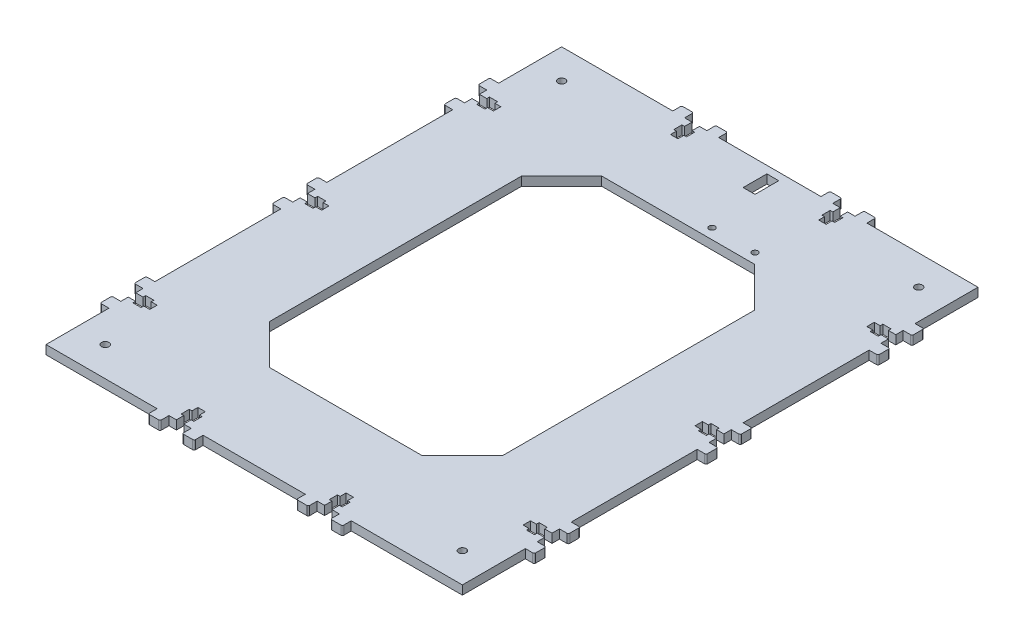
SolidWorks part; units mm, degrees
ref_plane "Plan de face" through (0, 0, 0) normal (0, 0, 1) x (1, 0, 0)
ref_plane "Plan de dessus" through (0, 0, 0) normal (0, 1, 0) x (1, 0, 0)
ref_plane "Plan de droite" through (0, 0, 0) normal (1, 0, 0) x (0, 0, -1)
sketch "Esquisse2" plane through (0, 0, 0) normal (0, 1, 0) x (1, 0, 0)
  line L16 (0, 0) -> (0, -31.3635) construction
  line L23 (-140.5, 174) -> (0, 174)
  line L24 (-140.5, 174) -> (-140.5, 0)
  line L25 (-140.5, 0) -> (-78.5, 0)
  line L26 (0, 174) -> (0, 112)
  line L27 (-140.5, 174) -> (0, 0) construction
  line L28 (-140.5, 0) -> (0, 174) construction
  line L29 (0, 0) -> (25.964, 0) construction
  line L30 (0, 112) -> (-78.5, 112)
  line L31 (-78.5, 112) -> (-78.5, 0)
  circle A4 centre (-120.5, 154) radius 2.5
  point P28 (-70.25, 87)
  dimension "D11" = 348
  dimension "D17" = 5
  dimension "D8" = 20
  dimension "D9" = 20
  dimension "D10" = 281
  dimension "D16" = 62
extrude "plaque" add sketch "Esquisse2" along normal mid plane 6
sketch "Esquisse10" plane through (0, 3, 0) normal (0, 1, 0) x (1, 0, 0)
  line L0 (-140.5, 174) -> (-140.5, 0) construction
  line L2 (0, 174) -> (-140.5, 174) construction
  line B0 (-140.5, 100.5) -> (-145.5, 100.5)
  line B1 (-146.5, 101.5) -> (-146.5, 107.5)
  line B2 (-145.5, 108.5) -> (-140.5, 108.5)
  line B3 (-140.5, 108.5) -> (-140.5, 113.5)
  line B4 (-140.5, 113.5) -> (-135.5, 113.5)
  line B5 (-135.5, 113.5) -> (-135.5, 111.7)
  line B6 (-135.5, 111.7) -> (-130, 111.7)
  line B7 (-130, 111.7) -> (-130, 113.5)
  line B8 (-130, 113.5) -> (-126, 113.5)
  line B9 (-126, 113.5) -> (-126, 118.5)
  line B10 (-126, 116) -> (-140.5, 116) construction
  line B11 (-140.5, 131.5) -> (-140.5, 123.5)
  line B12 (-140.5, 108.5) -> (-140.5, 100.5)
  line B13 (-130, 118.5) -> (-126, 118.5)
  line B14 (-130, 120.3) -> (-130, 118.5)
  line B15 (-135.5, 120.3) -> (-130, 120.3)
  line B16 (-135.5, 118.5) -> (-135.5, 120.3)
  line B17 (-140.5, 118.5) -> (-135.5, 118.5)
  line B18 (-140.5, 123.5) -> (-140.5, 118.5)
  line B19 (-145.5, 123.5) -> (-140.5, 123.5)
  line B20 (-146.5, 130.5) -> (-146.5, 124.5)
  line B21 (-140.5, 131.5) -> (-145.5, 131.5)
  line B22 (-140.5, 113.5) -> (-140.5, 118.5)
  arc B23 (-146.5, 107.5) -> (-145.5, 108.5) centre (-145.5, 107.5) cw
  arc B24 (-145.5, 100.5) -> (-146.5, 101.5) centre (-145.5, 101.5) cw
  arc B25 (-145.5, 131.5) -> (-146.5, 130.5) centre (-145.5, 130.5) ccw
  arc B26 (-146.5, 124.5) -> (-145.5, 123.5) centre (-145.5, 124.5) ccw
  line B27 (-65.5, 174) -> (-65.5, 179)
  line B28 (-64.5, 180) -> (-58.5, 180)
  line B29 (-57.5, 179) -> (-57.5, 174)
  line B30 (-57.5, 174) -> (-52.5, 174)
  line B31 (-52.5, 174) -> (-52.5, 169)
  line B32 (-52.5, 169) -> (-54.3, 169)
  line B33 (-54.3, 169) -> (-54.3, 163.5)
  line B34 (-54.3, 163.5) -> (-52.5, 163.5)
  line B35 (-52.5, 163.5) -> (-52.5, 159.5)
  line B36 (-52.5, 159.5) -> (-47.5, 159.5)
  line B37 (-50, 159.5) -> (-50, 174) construction
  line B38 (-34.5, 174) -> (-42.5, 174)
  line B39 (-57.5, 174) -> (-65.5, 174)
  line B40 (-47.5, 163.5) -> (-47.5, 159.5)
  line B41 (-45.7, 163.5) -> (-47.5, 163.5)
  line B42 (-45.7, 169) -> (-45.7, 163.5)
  line B43 (-47.5, 169) -> (-45.7, 169)
  line B44 (-47.5, 174) -> (-47.5, 169)
  line B45 (-42.5, 174) -> (-47.5, 174)
  line B46 (-42.5, 179) -> (-42.5, 174)
  line B47 (-35.5, 180) -> (-41.5, 180)
  line B48 (-34.5, 174) -> (-34.5, 179)
  line B49 (-52.5, 174) -> (-47.5, 174)
  arc B50 (-58.5, 180) -> (-57.5, 179) centre (-58.5, 179) cw
  arc B51 (-65.5, 179) -> (-64.5, 180) centre (-64.5, 179) cw
  arc B52 (-34.5, 179) -> (-35.5, 180) centre (-35.5, 179) ccw
  arc B53 (-41.5, 180) -> (-42.5, 179) centre (-41.5, 179) ccw
  line M1 (-140.5, 174) -> (-140.5, 0)
  line M6 (0, 174) -> (-140.5, 174)
  dimension "D1" = 58
  dimension "D2" = 50
sketch_block_instance "Bloc4-17"
sketch_block "Bloc4" parameters "D7"=1, "D1"=5, "D2"=5, "D3"=5.5, "D4"=1.8, "D5"=4, "D6"=2.5
sketch_block_instance "Bloc4-29"
extrude "Boss.-Extru.8" add sketch "Esquisse10" against normal blind 6 contours B20 B26 B19 B21 B25 M1 | B24 B0 B2 B23 B1 M1 | B51 B27 B29 B50 B28 M6 | B47 B53 B46 B48 B52 M6 region at (-38.5, 3, -176.9749) region at (-61.5, 3, -176.9749) region at (-143.4749, 3, -127.5) region at (-143.4749, 3, -104.5)
extrude "Enlèv. mat.-Extru.8" cut sketch "Esquisse10<3>" against normal blind 6 contours B17 B4 B5 B6 B7 B8 B9 B13 B14 B15 B16 M1 | B44 B31 B32 B33 B34 B35 B36 B40 B41 B42 B43 M6 region at (-50, 3, -166.6427) region at (-133.1427, 3, -116)
sketch "Esquisse10<3>" plane through (0, 3, 0) normal (0, 1, 0) x (1, 0, 0) same geometry as "Esquisse10"
chamfer "Chanfrein1" distance 27 angle 45 1 edges at (-78.5, 0, -112)
mirror "Symétrie6" about plane through (-140.5, 3, 0) normal (0, 0, -1) of bodies 126 123
sketch "Esquisse13" plane through (0, 3, 0) normal (0, 1, 0) x (1, 0, 0)
  line L2 (-140.5, 100.5) -> (-140.5, -100.5) construction
  line B0 (-140.5, -15.5) -> (-145.5, -15.5)
  line B1 (-146.5, -14.5) -> (-146.5, -8.5)
  line B2 (-145.5, -7.5) -> (-140.5, -7.5)
  line B3 (-140.5, -7.5) -> (-140.5, -2.5)
  line B4 (-140.5, -2.5) -> (-135.5, -2.5)
  line B5 (-135.5, -2.5) -> (-135.5, -4.3)
  line B6 (-135.5, -4.3) -> (-130, -4.3)
  line B7 (-130, -4.3) -> (-130, -2.5)
  line B8 (-130, -2.5) -> (-126, -2.5)
  line B9 (-126, -2.5) -> (-126, 2.5)
  line B10 (-126, 0) -> (-140.5, 0) construction
  line B11 (-140.5, 15.5) -> (-140.5, 7.5)
  line B12 (-140.5, -7.5) -> (-140.5, -15.5)
  line B13 (-130, 2.5) -> (-126, 2.5)
  line B14 (-130, 4.3) -> (-130, 2.5)
  line B15 (-135.5, 4.3) -> (-130, 4.3)
  line B16 (-135.5, 2.5) -> (-135.5, 4.3)
  line B17 (-140.5, 2.5) -> (-135.5, 2.5)
  line B18 (-140.5, 7.5) -> (-140.5, 2.5)
  line B19 (-145.5, 7.5) -> (-140.5, 7.5)
  line B20 (-146.5, 14.5) -> (-146.5, 8.5)
  line B21 (-140.5, 15.5) -> (-145.5, 15.5)
  line B22 (-140.5, -2.5) -> (-140.5, 2.5)
  arc B23 (-146.5, -8.5) -> (-145.5, -7.5) centre (-145.5, -8.5) cw
  arc B24 (-145.5, -15.5) -> (-146.5, -14.5) centre (-145.5, -14.5) cw
  arc B25 (-145.5, 15.5) -> (-146.5, 14.5) centre (-145.5, 14.5) ccw
  arc B26 (-146.5, 8.5) -> (-145.5, 7.5) centre (-145.5, 8.5) ccw
sketch_block_instance "Bloc4-35"
extrude "Boss.-Extru.10" add sketch "Esquisse13" against normal blind 6 contours B24 B0 B12 B2 B23 B1 | B20 B26 B19 B11 B21 B25 region at (-143.4749, 3, -11.5) region at (-143.4749, 3, 11.5)
extrude "Enlèv. mat.-Extru.10" cut sketch "Esquisse13<3>" against normal blind 6 contours B22 B4 B5 B6 B7 B8 B9 B13 B14 B15 B16 B17 region at (-133.1427, 3, 0)
sketch "Esquisse13<3>" plane through (0, 3, 0) normal (0, 1, 0) x (1, 0, 0) same geometry as "Esquisse13"
mirror "Symétrie5" about plane through (0, 3, -174) normal (-1, 0, 0) of bodies 136 122
sketch "Esquisse14" plane through (0, -3, 0) normal (0, -1, 0) x (-1, 0, 0)
  line L0 (-16, 119) -> (-45, 119) construction
  line L1 (-3, 153) -> (-11, 153)
  line L2 (-3, 153) -> (-3, 169)
  line L3 (-3, 169) -> (-11, 169)
  line L4 (-11, 153) -> (-11, 169)
  line L5 (-3, 153) -> (-11, 169) construction
  line L6 (-3, 169) -> (-11, 153) construction
  line L7 (-34.5, 174) -> (34.5, 174) construction
  line L8 (0, 174) -> (0, 112) construction
  line L9 (51.5, 112) -> (-51.5, 112) construction
  circle A0 centre (-16, 119) radius 2
  circle A1 centre (-45, 119) radius 2
  point P0 (-7, 161)
  dimension "D3" = 4
  dimension "D1" = 8
  dimension "D2" = 16
  dimension "D4" = 29
  dimension "D5" = 55
  dimension "D6" = 16
  dimension "D7" = 7
  dimension "D8" = 13
extrude "Enlèv. mat.-Extru.11" cut sketch "Esquisse14" against normal up to next
equation "\"W\"= \"W@Prusa i4.2.sldasm\""
equation "\"D1@Esquisse10\"=\"L\"/6"
equation "\"L\"= \"L@Prusa i4.2.sldasm\""
equation "\"D10@Esquisse2\"= \"W\" - 19"
equation "\"D11@Esquisse2\"=\"L\""
equation "\"D2@Esquisse10\"=\"W\"/6"
